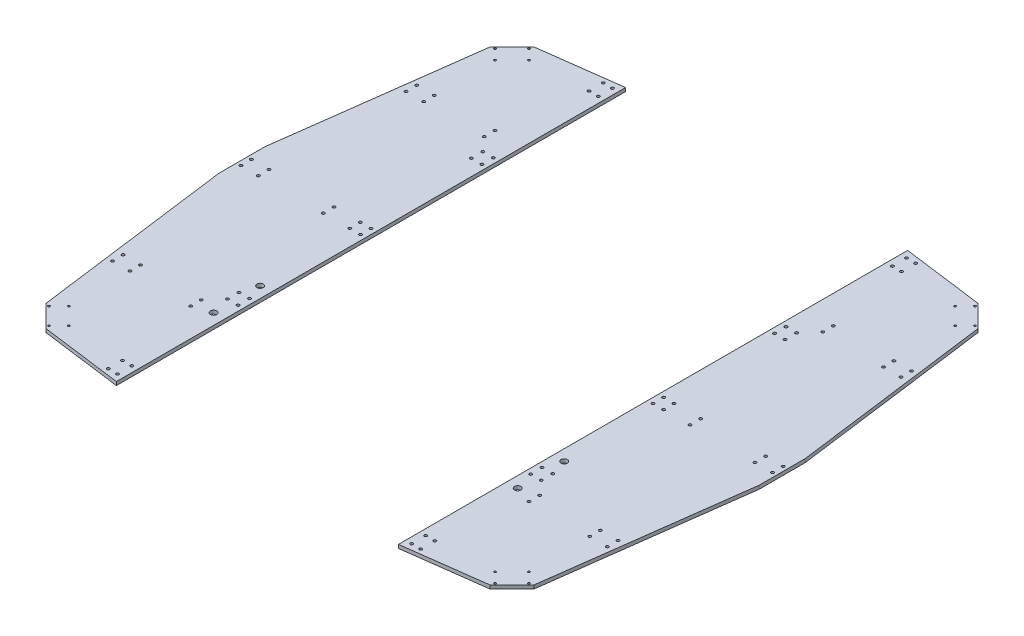
SolidWorks part; units mm, degrees
ref_plane "前视基准面" through (0, 0, 0) normal (0, 0, 1) x (1, 0, 0)
ref_plane "上视基准面" through (0, 0, 0) normal (0, 1, 0) x (1, 0, 0)
ref_plane "右视基准面" through (0, 0, 0) normal (1, 0, 0) x (0, 0, -1)
other "Configuration Table"
sketch "草图1" plane through (0, 0, 0) normal (0, 1, 0) x (1, 0, 0)
  line L0 (-314.9222, 345.9222) -> (-345.9222, 314.9222)
  line L5 (325, -325) -> (-325, 325) construction
  line L6 (325, 325) -> (-325, -325) construction
  line L7 (0, 325) -> (0, -325) construction
  line L8 (-383.07, 0) -> (383.0748, 0) construction
  line L9 (314.9222, 345.9222) -> (32.7201, 383.0748)
  line L10 (314.9222, 345.9222) -> (345.9222, 314.9222)
  line L11 (-383.07, 13.0001) -> (-230, 13.0001) construction
  line L12 (-314.9222, 345.9222) -> (-32.7201, 383.0748)
  line L13 (0, 325) -> (0, 399.6983)
  line L14 (-32.7201, 383.0748) -> (32.7201, 383.0748)
  line L15 (314.9222, -345.9222) -> (32.7201, -383.0748)
  line L16 (-32.7201, -383.0748) -> (32.7201, -383.0748)
  line L17 (-314.9222, -345.9222) -> (-32.7201, -383.0748)
  line L18 (-314.9222, -345.9222) -> (-345.9222, -314.9222)
  line L19 (-345.9222, 314.9222) -> (-383.0748, 32.7201)
  line L20 (-383.0748, -32.7201) -> (-383.0748, 32.7201)
  line L21 (-345.9222, -314.9222) -> (-383.0748, -32.7201)
  line L22 (-345.9222, -314.9222) -> (-314.9222, -345.9222)
  line L23 (345.9222, -314.9222) -> (314.9222, -345.9222)
  line L24 (345.9222, -314.9222) -> (383.0748, -32.7201)
  line L25 (383.0748, 32.7201) -> (383.0748, -32.7201)
  line L26 (345.9222, 314.9222) -> (383.0748, 32.7201)
  line L27 (-383.07, -12.9999) -> (-230, -12.9999) construction
  line L29 (361.6863, 195.182) -> (230, 195.182) construction
  line L30 (358.2633, 221.182) -> (230, 221.182) construction
  line L31 (-358.2633, 221.182) -> (-230, 221.182) construction
  line L32 (-361.6863, 195.182) -> (-230, 195.182) construction
  line L33 (361.6863, -195.182) -> (230, -195.182) construction
  line L34 (358.2633, -221.182) -> (230, -221.182) construction
  line L35 (-361.6863, -195.182) -> (-230, -195.182) construction
  line L36 (-358.2633, -221.182) -> (-230, -221.182) construction
  line L37 (-228, -357.3657) -> (-228, 357.3618) construction
  line L38 (-202, -360.7887) -> (-202, 360.7847) construction
  line L39 (383.07, 13.0001) -> (230, 13.0001) construction
  circle A5 centre (0, 0) radius 250
  circle A6 centre (302.1379, 326.1795) radius 1.5
  circle A7 centre (316.28, 340.3217) radius 1.5
  circle A8 centre (340.3217, 316.28) radius 1.5
  circle A9 centre (326.1795, 302.1379) radius 1.5
  circle A10 centre (302.1379, -326.1795) radius 1.5
  circle A11 centre (316.28, -340.3217) radius 1.5
  circle A12 centre (326.1795, -302.1379) radius 1.5
  circle A13 centre (340.3217, -316.28) radius 1.5
  circle A14 centre (-326.1795, -302.1379) radius 1.5
  circle A15 centre (-340.3217, -316.28) radius 1.5
  circle A16 centre (-302.1379, -326.1795) radius 1.5
  circle A17 centre (-316.28, -340.3217) radius 1.5
  circle A18 centre (-302.1379, 326.1795) radius 1.5
  circle A19 centre (-316.28, 340.3217) radius 1.5
  circle A20 centre (-326.1795, 302.1379) radius 1.5
  circle A21 centre (-340.3217, 316.28) radius 1.5
  circle A22 centre (350.9184, 215.682) radius 2
  circle A23 centre (377.0748, 7.5001) radius 2
  circle A24 centre (350.9184, 200.682) radius 2
  circle A25 centre (325.9184, 215.682) radius 2
  circle A26 centre (325.9184, 200.682) radius 2
  circle A27 centre (377.0748, -7.5951) radius 2
  circle A28 centre (352.0748, 7.5001) radius 2
  circle A29 centre (352.0748, -7.5951) radius 2
  circle A30 centre (350.9184, -200.682) radius 2
  circle A31 centre (350.9184, -215.682) radius 2
  circle A32 centre (325.9184, -200.682) radius 2
  circle A33 centre (325.9184, -215.682) radius 2
  circle A34 centre (-350.9184, -200.682) radius 2
  circle A35 centre (-325.9184, -200.682) radius 2
  circle A36 centre (-350.9184, -215.682) radius 2
  circle A37 centre (-325.9184, -215.682) radius 2
  circle A38 centre (-377.0748, 7.5001) radius 2
  circle A39 centre (-352.0748, 7.5001) radius 2
  circle A40 centre (-377.0748, -7.4999) radius 2
  circle A41 centre (-352.0748, -7.4999) radius 2
  circle A42 centre (-350.9184, 215.682) radius 2
  circle A43 centre (-350.9184, 200.682) radius 2
  circle A44 centre (-325.9184, 215.682) radius 2
  circle A45 centre (-325.9184, 200.682) radius 2
  circle A46 centre (-222.5, -164.8255) radius 2
  circle A47 centre (-207.5, -164.8255) radius 2
  circle A48 centre (-222.5, -181.0301) radius 2
  circle A49 centre (-207.5, -181.0301) radius 2
  circle A50 centre (-222.5, 181.0301) radius 2
  circle A51 centre (-207.5, 164.8255) radius 2
  circle A52 centre (-222.5, 164.8255) radius 2
  circle A53 centre (-207.5, 181.0301) radius 2
  circle A54 centre (207.5, -164.8255) radius 2
  circle A55 centre (222.5, -164.8255) radius 2
  circle A56 centre (207.5, -181.0301) radius 2
  circle A57 centre (222.5, -181.0301) radius 2
  circle A58 centre (207.5, 164.8255) radius 2
  circle A59 centre (222.5, 164.8255) radius 2
  circle A60 centre (207.5, 181.0301) radius 2
  circle A61 centre (222.5, 181.0301) radius 2
  circle A62 centre (-240, 215.682) radius 2
  circle A63 centre (-240, 200.682) radius 2
  circle A64 centre (-260, 7.5) radius 2
  circle A65 centre (-260, -7.5) radius 2
  circle A66 centre (-240, -200.682) radius 2
  circle A67 centre (-240, -215.682) radius 2
  circle A68 centre (240, -215.682) radius 2
  circle A69 centre (240, -200.682) radius 2
  circle A72 centre (240, 200.682) radius 2
  circle A73 centre (240, 215.682) radius 2
  circle A74 centre (207.5, 9.4052) radius 2
  circle A75 centre (222.5, 9.4052) radius 2
  circle A76 centre (207.5, -5.5948) radius 2
  circle A77 centre (222.5, -5.5948) radius 2
  circle A78 centre (-222.5, -5.5948) radius 2
  circle A79 centre (-207.5, -5.5948) radius 2
  circle A80 centre (-222.5, 9.4052) radius 2
  circle A81 centre (-207.5, 9.4052) radius 2
  circle A82 centre (260, -7.5) radius 2
  circle A83 centre (260, 7.5) radius 2
  circle A84 centre (215.6127, -141.5543) radius 4.5
  circle A85 centre (215.6127, -207.5543) radius 4.5
  circle A86 centre (-215.6127, -207.5543) radius 4.5
  circle A87 centre (-215.6127, -141.5543) radius 4.5
  point P0 (0, 0)
  point P13 (0, 383.0748)
  point P24 (-330.4222, -330.4222)
  point P75 (0, 0)
  dimension "D6" = 25
  dimension "D7" = 15
  dimension "D8" = 500
  dimension "D5" = 4
  dimension "D13" = 6
  dimension "D14" = 6
  dimension "D15" = 6
  dimension "D16" = 6
  dimension "D17" = 25
  dimension "D20" = 8
  dimension "D21" = 25
  dimension "D23" = 8
  dimension "D28" = 5.5
  dimension "D29" = 5.5
  dimension "D30" = 5.5
  dimension "D31" = 5.5
  dimension "D32" = 5.5
  dimension "D33" = 5.5
  dimension "D35" = 5.5
  dimension "D37" = 5.5
  dimension "D1" = 650
  dimension "D2" = 650
  dimension "D3" = 31
  dimension "D4" = 142.5
  dimension "D9" = 5.5
  dimension "D10" = 5.5
  dimension "D11" = 25
  dimension "D12" = 25
  dimension "D22" = 25
  dimension "D24" = 25
  dimension "D25" = 25
  dimension "D26" = 25
  dimension "D27" = 5.5
  dimension "D34" = 5.5
  dimension "D36" = 5.5
  dimension "D38" = 7.5001
  dimension "D39" = 7.4999
  dimension "D40" = 7.5
  dimension "D41" = 7.5
extrude "凸台-拉伸2" add sketch "草图1" along normal blind 5 contours L26 L10 L9 L14 L12 L0 L19 L20 L21 L18 L17 L16 L15 L23 L24 L25 | A13 L22 | L22 | A13 L18 region at (-172.4069, 0, -353.7562)
sketch "草图2" plane through (0, 5, 0) normal (0, 1, 0) x (1, 0, 0)
  line L0 (0, 0) -> (-330.4222, -330.4222) construction
  line L1 (0, 383.0748) -> (0, -383.0748)
  line L2 (-32.7201, 383.0748) -> (32.7201, 383.0748) construction
  line L3 (-32.7201, -383.0748) -> (32.7201, -383.0748) construction
  line L4 (-200, 361.052) -> (-200, -361.052)
  line L5 (-314.9222, 345.9222) -> (-32.7201, 383.0748) construction
  line L6 (-314.9222, -345.9222) -> (-32.7201, -383.0748) construction
  line L7 (200, 361.052) -> (200, -361.052)
  line L8 (314.9222, 345.9222) -> (32.7201, 383.0748) construction
  line L9 (314.9222, -345.9222) -> (32.7201, -383.0748) construction
  line L10 (-200, 361.052) -> (-200, 484.7149)
  line L11 (-200, 484.7149) -> (200, 484.7149)
  line L12 (200, 484.7149) -> (200, 361.052)
  line L13 (-200, -361.052) -> (-200, -418.819)
  line L14 (-200, -418.819) -> (200, -418.819)
  line L15 (200, -418.819) -> (200, -361.052)
  dimension "D1" = 200
  dimension "D2" = 200
extrude "切除-拉伸1" cut sketch "草图2" against normal blind 122 and the other way through all contours L4 L1 | L7 L1 | L7 L1 | L4 L1 | L0 L4 region at (-190.1188, 5, -422.8834)
sketch "草图3" plane through (0, 0, 0) normal (0, -1, 0) x (-1, 0, 0)
  circle A4 centre (208.5, -330.9223) radius 2
  circle A5 centre (221.5, -330.9223) radius 2
  circle A6 centre (221.5, -350.9223) radius 2
  circle A7 centre (208.5, -350.9223) radius 2
extrude "切除-拉伸2" cut sketch "草图3" along normal through all and the other way blind 39
sketch "草图4" plane through (0, 5, 0) normal (0, 1, 0) x (1, 0, 0)
  line L2 (-228, -357.3657) -> (-228, 357.3618) construction
  line L3 (-202, -360.7887) -> (-202, 360.7847) construction
  line L4 (-228, -357.3657) -> (-228, 357.3618)
  line L5 (-202, -360.7887) -> (-202, 360.7847)
  circle A8 centre (221.5, -330.9223) radius 2
  circle A9 centre (208.5, -330.9223) radius 2
  circle A10 centre (208.5, -350.9223) radius 2
  circle A11 centre (221.5, -350.9223) radius 2
  circle A15 centre (-208.5, -330.9223) radius 2
  circle A16 centre (-221.5, -330.9223) radius 2
  circle A17 centre (-208.5, -350.9223) radius 2
  circle A18 centre (-221.5, -350.9223) radius 2
  circle A19 centre (221.5, 350.9184) radius 2
  circle A20 centre (208.5, 350.9184) radius 2
  circle A21 centre (208.5, 330.9184) radius 2
  circle A22 centre (221.5, 330.9184) radius 2
  circle A23 centre (-208.5, 350.9184) radius 2
  circle A24 centre (-221.5, 350.9184) radius 2
  circle A25 centre (-221.5, 330.9184) radius 2
  circle A27 centre (-208.5, 330.9184) radius 2
extrude "切除-拉伸3" cut sketch "草图4" against normal through all and the other way blind 20 contours A16 | A15 | A17 | A18 | A11 | A10 | A9 | A8
sketch "草图5" plane through (0, 5, 0) normal (0, 1, 0) x (1, 0, 0)
  line L0 (-200, 150) -> (-200, -150)
  line L1 (200, 150) -> (200, -150)
  line L2 (-260, 7.5) -> (-260, -7.5) construction
  line L3 (-260, -7.5) -> (-200, -7.5) construction
  line L4 (-200, -7.5) -> (-200, 7.5)
  line L5 (-200, 7.5) -> (-260, 7.5) construction
  line L6 (-228, -357.3657) -> (-228, 357.3618) construction
  line L7 (-202, -360.7887) -> (-202, 360.7847) construction
  line L8 (0, 250) -> (0, -250) construction
  line L9 (-200, 361.048) -> (-200, -361.052) construction
  circle A0 centre (0, 0) radius 250
  circle A1 centre (-222.5, 7.5) radius 2
  circle A2 centre (-207.5, 7.5) radius 2
  circle A3 centre (-222.5, -7.5) radius 2
  circle A4 centre (-207.5, -7.5) radius 2
  circle A5 centre (207.5, -7.5) radius 2
  circle A6 centre (222.5, -7.5) radius 2
  circle A7 centre (207.5, 7.5) radius 2
  circle A8 centre (222.5, 7.5) radius 2
  arc M39 (-200, -150) -> (-200, 150) centre (0, 0) cw
  dimension "D1" = 5.5
  dimension "D2" = 5.5
  dimension "D3" = 5.5
  dimension "D4" = 5.5
extrude "凸台-拉伸3" add sketch "草图5" against normal blind 5 contours L0 M39 | L1 A0 region at (-220.2076, 5, 0) region at (220.2076, 5, 0)
sketch "草图6" plane through (0, 5, 0) normal (0, 1, 0) x (1, 0, 0)
  circle A0 centre (-208.5, 350.9184) radius 2
  circle A1 centre (-221.5, 350.9184) radius 2
  circle A2 centre (-221.5, 330.9184) radius 2
  circle A3 centre (-208.5, 330.9184) radius 2
  circle A4 centre (221.5, 350.9184) radius 2
  circle A5 centre (208.5, 350.9184) radius 2
  circle A6 centre (208.5, 330.9184) radius 2
  circle A7 centre (221.5, 330.9184) radius 2
extrude "切除-拉伸5" cut sketch "草图6" against normal blind 33
